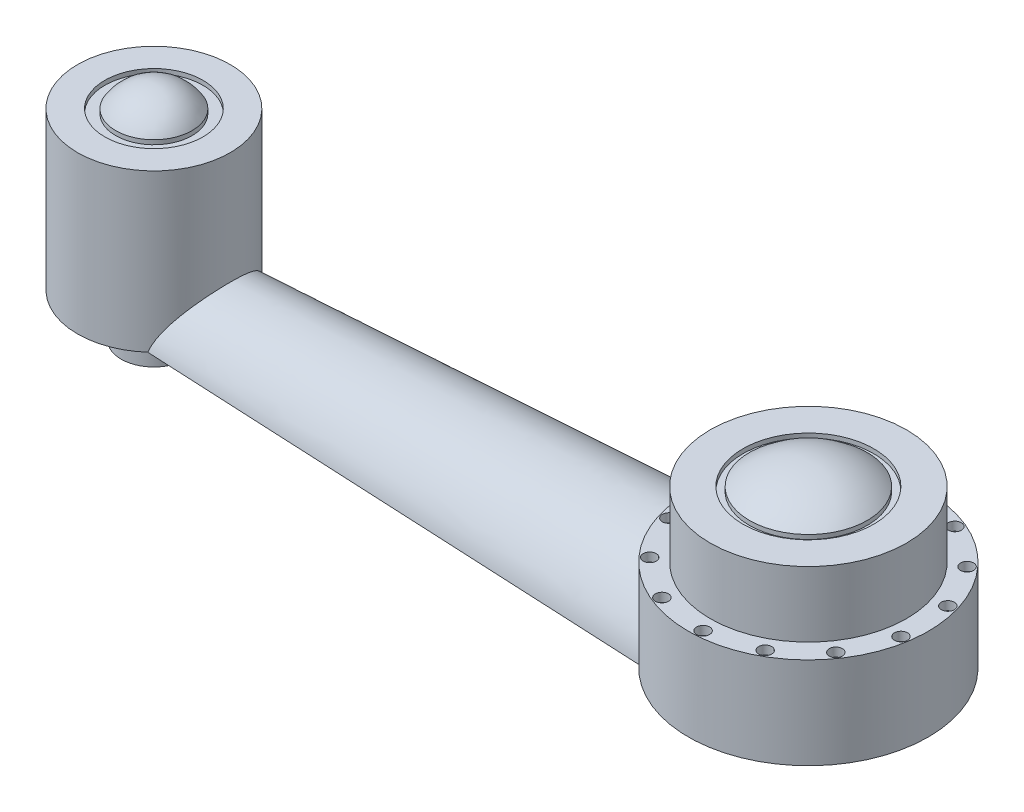
SolidWorks part; units mm, degrees
ref_plane "Ön Düzlem" through (0, 0, 0) normal (0, 0, 1) x (1, 0, 0)
ref_plane "Üst Düzlem" through (0, 0, 0) normal (0, 1, 0) x (1, 0, 0)
ref_plane "Sağ Düzlem" through (0, 0, 0) normal (1, 0, 0) x (0, 0, -1)
sketch "Çizim1" plane through (0, 0, 0) normal (0, 1, 0) x (1, 0, 0)
  circle A0 centre (0, 0) radius 55
  dimension "D1" = 110
  dimension "D2" = 110
extrude "Yükseklik-Ekstrüzyon1" add sketch "Çizim1" along normal blind 42
sketch "Çizim4" plane through (0, 42, 0) normal (0, 1, 0) x (1, 0, 0)
  circle A0 centre (0, 0) radius 45
  dimension "D1" = 90
extrude "Yükseklik-Ekstrüzyon2" add sketch "Çizim4" along normal blind 30
sketch "Çizim5" plane through (0, 72, 0) normal (0, 1, 0) x (1, 0, 0)
  circle A0 centre (0, 0) radius 30
  circle A1 centre (0, 0) radius 27
  dimension "D1" = 60
  dimension "D2" = 3
extrude "Kes-Ekstrüzyon1" cut sketch "Çizim5" against normal blind 2
sketch "Çizim6" plane through (0, 72, 0) normal (0, 1, 0) x (1, 0, 0)
  line L0 (0, 0) -> (-300, 0) construction
  circle A0 centre (-300, 0) radius 35
  dimension "D2" = 70
  dimension "D1" = 300
extrude "Yükseklik-Ekstrüzyon3" add sketch "Çizim6" against normal blind 72 separate body
sketch "Çizim7" plane through (0, 72, 0) normal (0, 1, 0) x (1, 0, 0)
  circle A2 centre (-300, 0) radius 22.5
  circle A3 centre (-300, 0) radius 17.5
  dimension "D1" = 45
  dimension "D2" = 5
extrude "Kes-Ekstrüzyon2" cut sketch "Çizim7" against normal blind 2
ref_plane "Düzlem1" through (-300, 0, 0) normal (1, 0, 0) x (0, 0, -1)
sketch "Çizim16" plane through (-300, 0, 0) normal (1, 0, 0) x (0, 0, -1)
  line L0 (-25, 0) -> (25, 0)
  arc A0 (-25, 0) -> (25, 0) centre (0, -7.1414) cw
  point P4 (0, 0)
  dimension "D2" = 26
  dimension "D1" = 50
sketch "Çizim17" plane through (0, 0, 0) normal (1, 0, 0) x (0, 0, -1)
  line L0 (-39.5, 0) -> (39.5, 0)
  arc A0 (-39.5, 0) -> (39.5, 0) centre (0, -6.3048) cw
  point P3 (0, 0)
  dimension "D1" = 40
  dimension "D2" = 79
loft "Loft1" add profiles "Çizim17", "Çizim16"
sketch "Çizim18" plane through (0, 42, 0) normal (0, 1, 0) x (1, 0, 0)
  circle A0 centre (0, 0) radius 51.5 construction
  circle A1 centre (-25.1474, 44.9428) radius 3
  circle A2 centre (0, 0) radius 51.5 construction
  circle A3 centre (-3.157, 51.4031) radius 3
  circle A4 centre (0, 0) radius 51.5 construction
  circle A5 centre (19.4586, 47.6824) radius 3
  circle A6 centre (0, 0) radius 51.5 construction
  circle A7 centre (38.2202, 34.5176) radius 3
  circle A8 centre (0, 0) radius 51.5 construction
  circle A9 centre (49.4119, 14.5162) radius 3
  circle A10 centre (0, 0) radius 51.5 construction
  circle A11 centre (50.8169, -8.3604) radius 3
  circle A12 centre (0, 0) radius 51.5 construction
  circle A13 centre (42.157, -29.5811) radius 3
  circle A14 centre (0, 0) radius 51.5 construction
  circle A15 centre (25.1474, -44.9428) radius 3
  circle A16 centre (0, 0) radius 51.5 construction
  circle A17 centre (3.157, -51.4031) radius 3
  circle A18 centre (0, 0) radius 51.5 construction
  circle A19 centre (-19.4586, -47.6824) radius 3
  circle A20 centre (0, 0) radius 51.5 construction
  circle A21 centre (-38.2202, -34.5176) radius 3
  circle A22 centre (0, 0) radius 51.5 construction
  circle A23 centre (-49.4119, -14.5162) radius 3
  circle A24 centre (0, 0) radius 51.5 construction
  circle A25 centre (-50.8169, 8.3604) radius 3
  circle A26 centre (0, 0) radius 51.5 construction
  circle A27 centre (-42.157, 29.5811) radius 3
  point P47 (0, 0)
  dimension "D1" = 103
  dimension "D2" = 6
  dimension "D3" = 14
extrude "Kes-Ekstrüzyon3" cut sketch "Çizim18" against normal blind 4
dome "Kubbe1" faces to dome 1 distance 10 reverse direction no elliptical dome no face at (-300, 72, 17.5) parameters "D1"=10
dome "Kubbe2" faces to dome 1 distance 10 reverse direction no elliptical dome no face at (0, 72, 27) parameters "D1"=10
sketch "Çizim19" plane through (0, 0, 0) normal (0, -1, 0) x (1, 0, 0)
  circle A0 centre (-300, 0) radius 15
  circle A1 centre (0, 0) radius 15
  dimension "D1" = 30
  dimension "D2" = 30
extrude "Yükseklik-Ekstrüzyon4" add sketch "Çizim19" along normal blind 20
